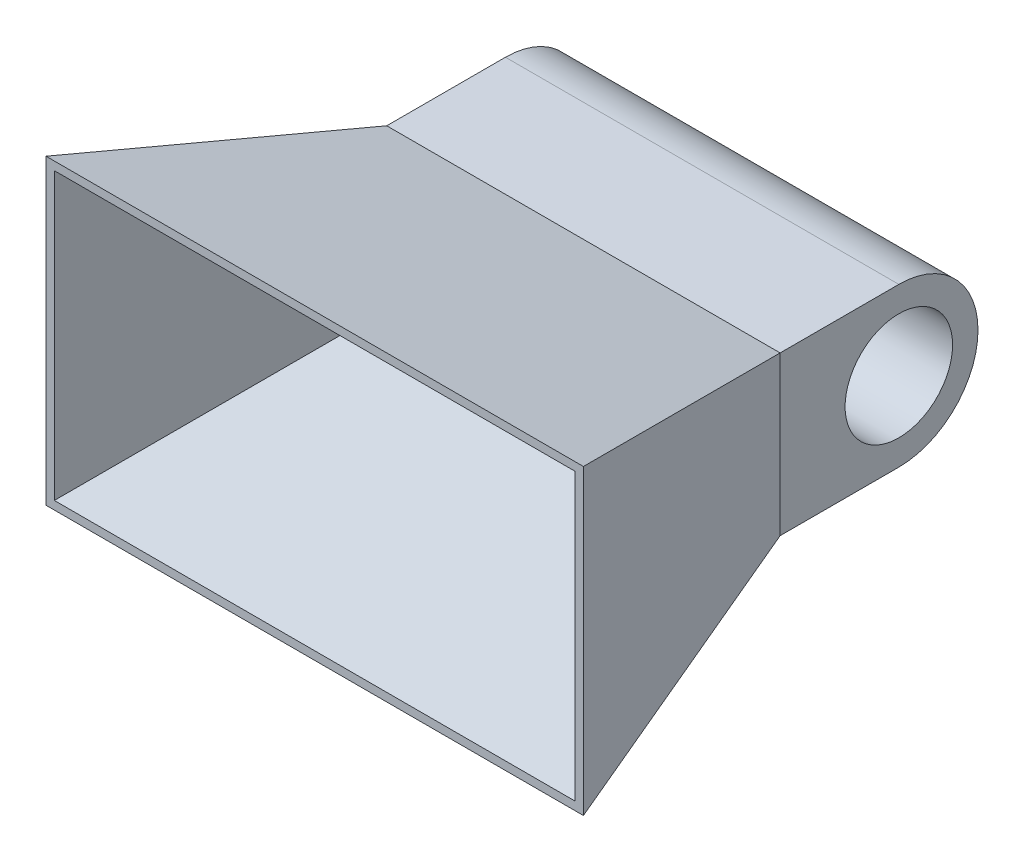
SolidWorks part; units mm, degrees
ref_plane "Front Plane" through (0, 0, 0) normal (0, 0, 1) x (1, 0, 0)
ref_plane "Top Plane" through (0, 0, 0) normal (0, 1, 0) x (1, 0, 0)
ref_plane "Right Plane" through (0, 0, 0) normal (1, 0, 0) x (0, 0, -1)
sketch "Camera Cone Sketch" plane through (0, 0, 0) normal (0, 0, 1) x (1, 0, 0)
  line L1 (-100, 56.25) -> (100, 56.25)
  line L2 (-100, 56.25) -> (-100, -56.25)
  line L3 (-100, -56.25) -> (100, -56.25)
  line L4 (100, 56.25) -> (100, -56.25)
  line L5 (-100, 56.25) -> (100, -56.25) construction
  line L6 (-100, -56.25) -> (100, 56.25) construction
  point P0 (0, 0)
  dimension "Camera Height" = 112.5
  dimension "Camera Width" = 200
extrude "Camera Cone Extrude" add sketch "Camera Cone Sketch" against normal blind 100 draft 15
shell "Camera Cone Shell" thickness 3 removed face at (0, 0, 0)
ref_plane "Lefthand Plane" through (73.2051, 0, 0) normal (1, 0, 0) x (0, 0, -1)
ref_plane "Righthand Plane" through (-73.2051, 0, 0) normal (-1, 0, 0) x (0, 0, 1)
sketch "Hinge Sketch" plane through (73.2051, 0, 0) normal (1, 0, 0) x (0, 0, -1)
  line L0 (144.1826, 29.4551) -> (144.1826, -29.4551) construction
  line L1 (100, 29.4551) -> (144.1826, 29.4551)
  line L2 (100, 29.4551) -> (100, -29.4551)
  line L3 (100, -29.4551) -> (144.1826, -29.4551)
  line L4 (144.1826, 29.4551) -> (144.1826, -29.4551) construction
  line L5 (114.7275, 0) -> (114.7275, 29.4551) construction
  line L6 (114.7275, 14.7275) -> (144.1826, 14.7275) construction
  line L7 (100, -29.4551) -> (100, 29.4551) construction
  line L8 (114.7275, 0) -> (114.7275, -29.4551) construction
  line L9 (129.4551, 29.4551) -> (129.4551, -29.4551) construction
  line L10 (114.7275, 0) -> (100, 0) construction
  line L11 (129.4551, 0) -> (144.1826, 0) construction
  line L12 (129.4551, 0) -> (114.7275, 0) construction
  line L13 (144.1826, 29.4551) -> (100, -29.4551) construction
  line L14 (144.1826, 0) -> (173.6377, 0) construction
  arc A0 (144.1826, -29.4551) -> (144.1826, 29.4551) centre (144.1826, 0) ccw
extrude "Hinge Extrude" add sketch "Hinge Sketch" against normal up to surface (146.4102 mm away) up to plane "Righthand Plane"
sketch "Hinge Hole Sketch" plane through (73.2051, 0, 0) normal (1, 0, 0) x (0, 0, -1)
  circle A0 centre (144.1826, 0) radius 20
  arc A1 (144.1826, -29.4551) -> (144.1826, 29.4551) centre (144.1826, 0) ccw construction
  dimension "D2" = 40
extrude "Hinge Hole Cut" cut sketch "Hinge Hole Sketch" against normal up to surface (146.4102 mm away) up to face at (-73.2051, 0, -129.4551)
equation "\"Camera Width\"= 200mm"
equation "\"Camera Height\"= \"Camera Width\" * ( 9 / 16 )"
